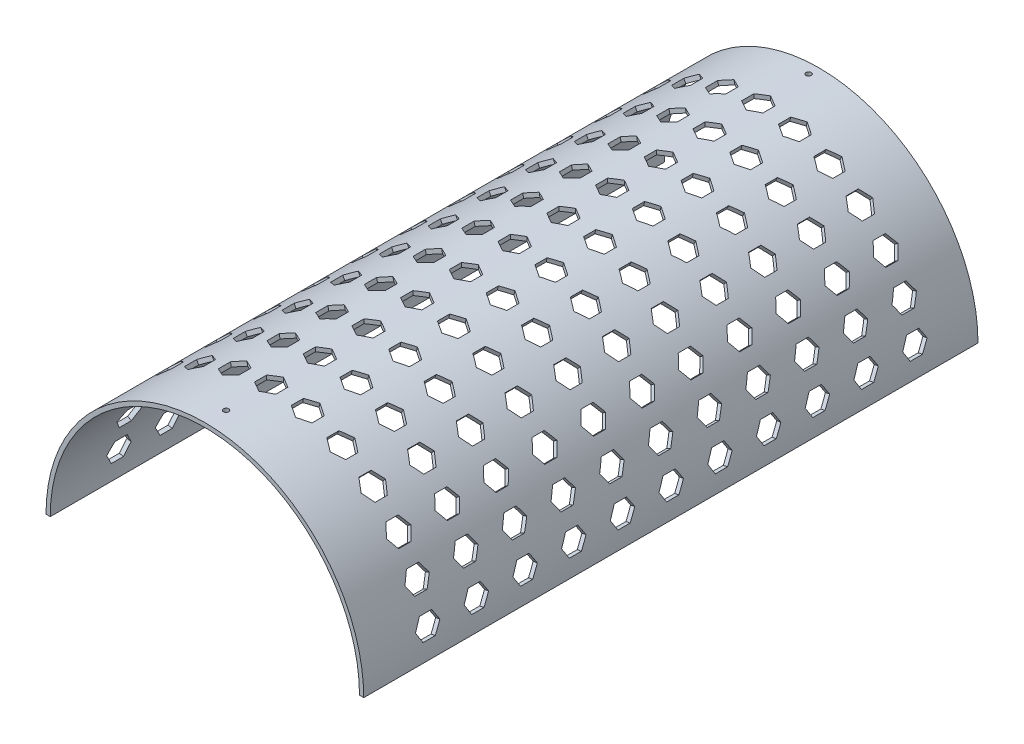
SolidWorks part; units mm, degrees
material "PET"
ref_plane "Front Plane" through (0, 0, 0) normal (0, 0, 1) x (1, 0, 0)
ref_plane "Top Plane" through (0, 0, 0) normal (0, 1, 0) x (1, 0, 0)
ref_plane "Right Plane" through (0, 0, 0) normal (1, 0, 0) x (0, 0, -1)
sketch "Sketch1" plane through (0, 0, 0) normal (0, 0, 1) x (1, 0, 0)
  line L0 (-75, 0) -> (-73, 0)
  line L1 (-73, 0) -> (73, 0) construction
  line L2 (73, 0) -> (75, 0)
  arc A0 (75, 0) -> (-75, 0) centre (0, 0) ccw
  arc A1 (73, 0) -> (-73, 0) centre (0, 0) ccw
  arc A2 (-75, 0) -> (75, 0) centre (0, 0) ccw construction
  circle A3 centre (0, 0) radius 75 construction
  arc A4 (-73, 0) -> (73, 0) centre (0, 0) ccw construction
  circle A5 centre (0, 0) radius 73 construction
  dimension "D1" = 150
  dimension "D2" = 2
extrude "Boss-Extrude1" add sketch "Sketch1" along normal blind 290
sketch "Sketch4" plane through (0, 0, 0) normal (0, 1, 0) x (1, 0, 0)
  line L0 (-75, -290) -> (75, -290) construction
  line L1 (75, 0) -> (-75, 0) construction
  circle A0 centre (0, -5) radius 1.25
  circle A1 centre (0, -280) radius 1.25
  dimension "D1" = 2.5
  dimension "D3" = 2.5
  dimension "D2" = 10
  dimension "D4" = 5
extrude "Cut-Extrude2" cut sketch "Sketch4" along normal up to surface (75 mm away) up to face at (0, 37.5, 145)
sketch "Sketch2" plane through (0, 0, 0) normal (0, 1, 0) x (1, 0, 0)
  line L0 (0, 0) -> (0, -28.6927) construction
  line L1 (5, -31.5794) -> (5, -25.8059)
  line L2 (5, -25.8059) -> (0, -22.9192)
  line L3 (0, -22.9192) -> (-5, -25.8059)
  line L4 (-5, -25.8059) -> (-5, -31.5794)
  line L5 (-5, -31.5794) -> (0, -34.4662)
  line L6 (0, -34.4662) -> (5, -31.5794)
  circle A1 centre (0, -28.6927) radius 5 construction
  dimension "D1" = 10
extrude "Cut-Extrude3" cut sketch "Sketch2" along normal up to surface (74.8331 mm away) up to face at (0, 37.5, 145)
pattern_circular "CirPattern1" count 7 every 13.333 about axis through (0, 0, 290) along (0, 0, -1) of "Cut-Extrude3" reverse direction yes other way count 7
pattern_linear "LPattern1" count 11 spacing 23 along (0, 0, 1) of "CirPattern1", "Cut-Extrude3"
